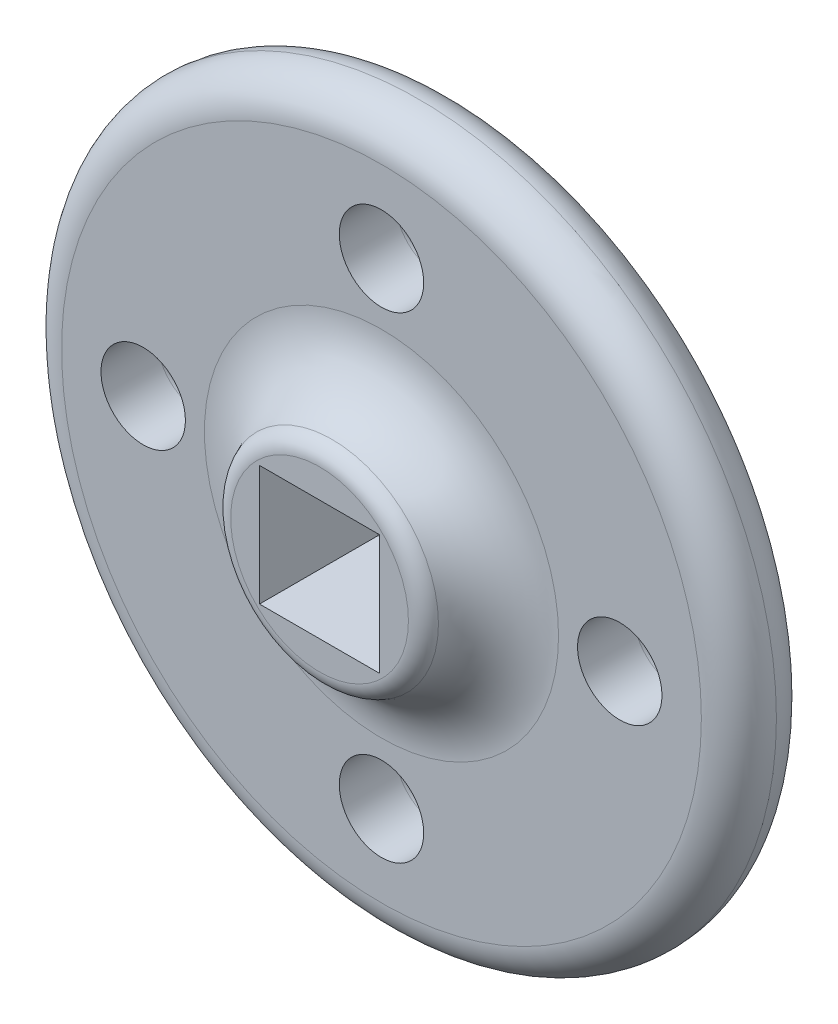
SolidWorks part; units mm, degrees
ref_plane "Front Plane" through (0, 0, 0) normal (0, 0, 1) x (1, 0, 0)
ref_plane "Top Plane" through (0, 0, 0) normal (0, 1, 0) x (1, 0, 0)
ref_plane "Right Plane" through (0, 0, 0) normal (1, 0, 0) x (0, 0, -1)
sketch "Sketch1" plane through (0, 0, 0) normal (0, 0, 1) x (1, 0, 0)
  line L1 (3.2, 3.2) -> (-3.2, 3.2)
  line L2 (3.2, 3.2) -> (3.2, -3.2)
  line L3 (3.2, -3.2) -> (-3.2, -3.2)
  line L4 (-3.2, 3.2) -> (-3.2, -3.2)
  line L5 (3.2, 3.2) -> (-3.2, -3.2) construction
  line L6 (3.2, -3.2) -> (-3.2, 3.2) construction
  circle A1 centre (12.7, 0) radius 2.25
  circle A2 centre (0, -12.7) radius 2.25
  circle A3 centre (-12.7, 0) radius 2.25
  circle A4 centre (0, 12.7) radius 2.25
  circle A5 centre (0, 0) radius 19.05
  circle A6 centre (0, 0) radius 5.5
  point P0 (0, 0)
  dimension "D2" = 4.5
  dimension "D5" = 38.1
  dimension "D6" = 11
  dimension "D1" = 6.4
  dimension "D3" = 12.7
  dimension "D4" = 4
extrude "Boss-Extrude1" add sketch "Sketch1" along normal blind 4 contours A5 A6 A1 A2 A3 A4 | A6 L4 L1 L2 L3 region at (-18.5112, 0, 0) region at (-5.3444, 0, 0)
extrude "Boss-Extrude2" add sketch "Sketch1<3>" along normal blind 3.3 from surface contours A6 L4 L1 L2 L3 region at (-5.3444, 0, 0) starting at face at (14.95, 0, 4)
sketch "Sketch1<3>" plane through (0, 0, 0) normal (0, 0, 1) x (1, 0, 0) same geometry as "Sketch1"
fillet "Fillet1" radius 4 1 edges at (5.5, 0, 4)
fillet "Fillet2" radius 1 1 edges at (5.5, 0, 7.3)
fillet "Fillet3" radius 2 2 edges at (19.05, 0, 0) (19.05, 0, 4)
fillet "Fillet4" radius 1 8 edges at (2.25, -12.7, 0) (-10.45, 0, 0) (3.2, 0, 0) (0, 3.2, 0) (-3.2, 0, 0) (0, -3.2, 0) (14.95, 0, 0) (2.25, 12.7, 0)
